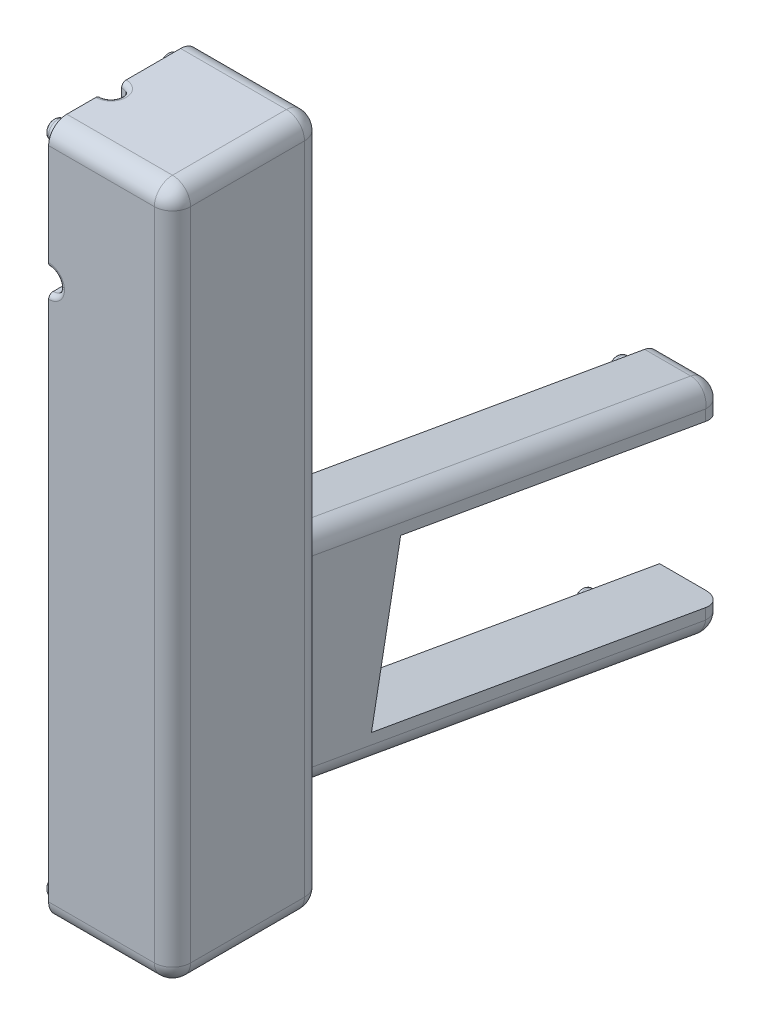
SolidWorks part; units mm, degrees
ref_plane "Front Plane" through (0, 0, 0) normal (0, 0, 1) x (1, 0, 0)
ref_plane "Top Plane" through (0, 0, 0) normal (0, 1, 0) x (1, 0, 0)
ref_plane "Right Plane" through (0, 0, 0) normal (1, 0, 0) x (0, 0, -1)
sketch "Sketch1" plane through (0, 0, 0) normal (0, 1, 0) x (1, 0, 0)
  line L1 (0, 0) -> (27.305, 0)
  line L2 (0, 0) -> (0, 33.1)
  line L3 (0, 33.1) -> (27.305, 33.1)
  line L4 (27.305, 0) -> (27.305, 33.1)
  dimension "D1" = 27.305
  dimension "D2" = 33.1
extrude "Boss-Extrude1" add sketch "Sketch1" along normal blind 152.4
sketch "Sketch2" plane through (0, 0, 0) normal (-1, 0, 0) x (0, 0, 1)
  line L0 (0, 152.4) -> (0, 0) construction
  line L1 (-6.35, 146.05) -> (-26.75, 146.05)
  line L2 (-6.35, 146.05) -> (-6.35, 6.35)
  line L3 (-6.35, 6.35) -> (-26.75, 6.35)
  line L4 (-26.75, 146.05) -> (-26.75, 6.35)
  line L5 (-33.1, 152.4) -> (0, 152.4) construction
  line L6 (-33.1, 152.4) -> (-33.1, 0) construction
  line L7 (-33.1, 0) -> (0, 0) construction
  dimension "D1" = 6.35
  dimension "D2" = 6.35
  dimension "D3" = 6.35
  dimension "D4" = 6.35
extrude "Cut-Extrude1" cut sketch "Sketch2" against normal blind 19.05
sketch "Sketch3" plane through (0, 0, 0) normal (0, 0, 1) x (1, 0, 0)
  line L0 (0, 152.4) -> (0, 0) construction
  line L1 (0, 125.055) -> (0, 120.055)
  arc A0 (0, 125.055) -> (0, 120.055) centre (0, 122.555) cw
  dimension "D1" = 29.845
extrude "HitLED" cut sketch "Sketch3" against normal up to next
sketch "Sketch6" plane through (19.05, 0, 0) normal (-1, 0, 0) x (0, 0, 1)
  line L0 (-15.7, 107.95) -> (-15.7, 33.02)
  line L1 (-9.35, 107.95) -> (-23.75, 107.95)
  line L2 (-9.35, 107.95) -> (-9.35, 33.02)
  line L3 (-9.35, 33.02) -> (-23.75, 33.02)
  line L4 (-23.75, 107.95) -> (-23.75, 33.02)
  line L5 (-17.4, 33.02) -> (-17.4, 107.95)
  line L7 (-6.35, 146.05) -> (-26.75, 146.05) construction
  line L8 (-26.75, 146.05) -> (-26.75, 6.35) construction
  line M8 (-6.35, 146.05) -> (-26.75, 146.05)
  dimension "D1" = 38.1
  dimension "D2" = 3
  dimension "D3" = 1.7
  dimension "D4" = 6.35
  dimension "D5" = 6.35
  dimension "D6" = 74.93
extrude "PCB" add sketch "Sketch6" along normal blind 6.35 contours L3 L2 L0 M8 | L3 L5 L1 L4 region at (19.05, 70.485, -12.525) region at (19.05, 70.485, -20.575)
sketch "Sketch16" plane through (0, 0, 0) normal (-1, 0, 0) x (0, 0, 1)
  line L1 (-33.1, 152.4) -> (0, 152.4) construction
  line L2 (0, 120.055) -> (0, 0) construction
  line L3 (-33.1, 0) -> (0, 0) construction
  line L5 (-33.1, 152.4) -> (-33.1, 0) construction
  circle A0 centre (-4, 148.4) radius 2
  circle A1 centre (-4, 4) radius 2
  circle A2 centre (-29.1, 148.4) radius 2
  circle A3 centre (-29.1, 4) radius 2
  dimension "D1" = 4
  dimension "D3" = 4
  dimension "D2" = 4
  dimension "D4" = 4
extrude "PressFit" add sketch "Sketch16" along normal blind 3
fillet "Fillet-PressFit" radius 1 4 edges at (-3, 4, -27.1) (-3, 4, -2) (-3, 148.4, -27.1) (-3, 148.4, -2)
sketch "Sketch23" plane through (0, 0, -25.4) normal (-1, 0, 0) x (0, 0, 1)
  line L4 (-7.7, 61.1358) -> (-7.7, 12.7)
  line L5 (-7.7, 12.7) -> (-109.3, -5.2148)
  line L6 (-109.3, -5.2148) -> (-109.3, 43.221)
  line L7 (-109.3, 43.221) -> (-7.7, 61.1358)
  dimension "D1" = 47.7
  dimension "D2" = 12.7
extrude "Butt" add sketch "Sketch23" against normal blind 14.175
sketch "Sketch20" plane through (0, 0, 0) normal (-1, 0, 0) x (0, 0, 1)
  line L0 (-63.4356, 49.3389) -> (-57.0033, 14.9332)
  line L1 (-63.4356, 49.3389) -> (-130.4061, 37.5302)
  line L2 (-57.0033, 14.9332) -> (-123.9738, 3.1245)
  line L6 (-130.4061, 37.5302) -> (-134.7, 36.7731)
  line L10 (-123.9738, 3.1245) -> (-134.7, 1.2331)
  line L11 (-134.7, 1.2331) -> (-134.7, 36.7731)
  dimension "D2" = 35
extrude "BatteryPack" cut sketch "Sketch20" against normal blind 14.175
sketch "Sketch22" plane through (0, 0, 0) normal (-1, 0, 0) x (0, 0, 1)
  line L0 (-63.4356, 49.3389) -> (-134.7, 36.7731) construction
  line L2 (-134.7, 1.2331) -> (-57.0033, 14.9332) construction
  line L4 (-57.0033, 14.9332) -> (-63.4356, 49.3389) construction
  circle A0 centre (-128.067, 41.1666) radius 2
  circle A1 centre (-120.4429, 0.5231) radius 2
  dimension "D1" = 3.175
  dimension "D2" = 3.175
  dimension "D3" = 65.0325
  dimension "D4" = 65.0073
extrude "PressFit - Bottom" add sketch "Sketch22" along normal blind 3
sketch "Sketch25" plane through (0, 146.05, 0) normal (0, -1, 0) x (1, 0, 0)
  line L0 (0, -6.35) -> (0, -26.75) construction
  line L1 (0, -11.4) -> (0, -16.1)
  line L2 (19.05, -26.75) -> (0, -26.75) construction
  arc A0 (0, -11.4) -> (0, -16.1) centre (0, -13.75) cw
  dimension "D1" = 13
extrude "IRLED" cut sketch "Sketch25" against normal up to next
fillet "Fillet - Body" radius 4 17 edges at (14.175, -1.9908, -134.7) (14.175, 39.997, -134.7) (7.0875, 43.221, -134.7) (7.0875, -5.2148, -134.7) (14.175, 52.1784, -83.9) (14.175, 3.7426, -83.9) (7.0875, 12.7, -33.1) (14.175, 36.9179, -33.1) (7.0875, 61.1358, -33.1) (13.6525, 152.4, -33.1) (13.6525, 152.4, 0) (27.305, 152.4, -16.55) (27.305, 76.2, -33.1) (27.305, 0, -16.55) (13.6525, 0, -33.1) (13.6525, 0, 0) (27.305, 76.2, 0)
fillet "Fillet-PressFit-Bottom" radius 1 2 edges at (-3, 0.5231, -118.4429) (-3, 41.1666, -126.067)
fillet "Fillet-LED's" radius 1 2 edges at (2.35, 152.4, -13.75) (2.5, 122.555, 0)
sketch "Sketch26" plane through (0, 0, 0) normal (-1, 0, 0) x (0, 0, 1)
  line L0 (-46.718, 58.7346) -> (-53.6116, 57.5191)
  line L1 (-53.6116, 57.5191) -> (-52.9865, 53.9738)
  line L2 (-52.9865, 53.9738) -> (-46.0928, 55.1893)
  line L3 (-46.0928, 55.1893) -> (-46.718, 58.7346)
  line L4 (-36.4054, 60.553) -> (-131.3946, 43.8039) construction
  point P6 (-46.4054, 56.962)
  dimension "D1" = 3.6
  dimension "D2" = 7
  dimension "D3" = 10
  dimension "D4" = 0
extrude "Cut-Extrude2" cut sketch "Sketch26" against normal blind 3.5
sketch "Sketch27" plane through (0, 0, 0) normal (-1, 0, 0) x (0, 0, 1)
  line L0 (-40.1594, 56.2356) -> (-58.92, 52.9276)
  line L1 (-58.92, 52.9276) -> (-58.6248, 51.2534)
  line L2 (-58.6248, 51.2534) -> (-39.8642, 54.5614)
  line L3 (-39.8642, 54.5614) -> (-40.1594, 56.2356)
  line L6 (-52.9865, 53.9738) -> (-46.0928, 55.1893) construction
  line L7 (-46.0928, 55.1893) -> (-46.718, 58.7346) construction
  dimension "D1" = 1.7
  dimension "D2" = 19.05
  dimension "D3" = 6.025
extrude "Cut-Extrude3" cut sketch "Sketch27" against normal blind 12.065
sketch "Sketch28" plane through (0, 0, 0) normal (-1, 0, 0) x (0, 0, 1)
  line L0 (-46.29, 53.4283) -> (-52.1989, 52.3864)
  line L1 (-46.29, 53.4283) -> (-41.9488, 28.8081)
  line L2 (-52.1989, 52.3864) -> (-47.8577, 27.7662)
  line L3 (-41.9488, 28.8081) -> (-47.8577, 27.7662)
  line L4 (-58.6248, 51.2534) -> (-39.8642, 54.5614) construction
  line L5 (-39.8642, 54.5614) -> (-40.1594, 56.2356) construction
  dimension "D1" = 6
  dimension "D2" = 6.525
  dimension "D3" = 25
extrude "Cut-Extrude4" cut sketch "Sketch28" against normal blind 7.825
